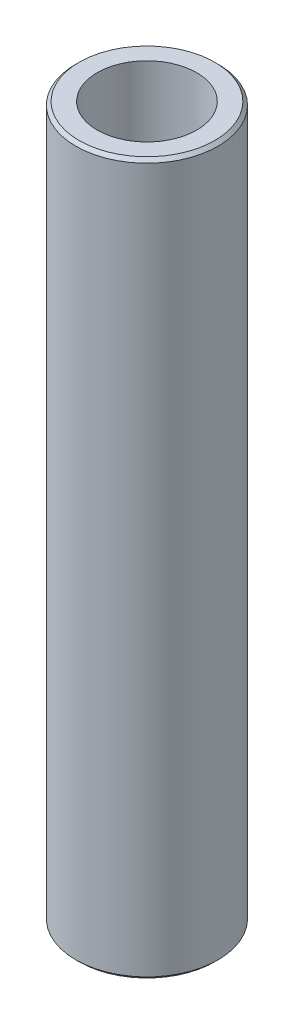
SolidWorks part; units mm, degrees
ref_plane "Front Plane" through (0, 0, 0) normal (0, 0, 1) x (1, 0, 0)
ref_plane "Top Plane" through (0, 0, 0) normal (0, 1, 0) x (1, 0, 0)
ref_plane "Right Plane" through (0, 0, 0) normal (1, 0, 0) x (0, 0, -1)
sketch "Sketch1" plane through (0, 0, 0) normal (0, 1, 0) x (1, 0, 0)
  circle A0 centre (0, 0) radius 60
  dimension "SHAFT_OD" = 120
extrude "Boss-Extrude1" add sketch "Sketch1" along normal blind 600
sketch "Sketch2" plane through (0, 0, 0) normal (0, 1, 0) x (1, 0, 0)
  circle A0 centre (0, 0) radius 41.98
  dimension "BORE_D" = 83.96
extrude "Cut-Extrude1" cut sketch "Sketch2" along normal through all
chamfer "Chamfer1" distance 2.7775 angle 45 2 edges at (0, 600, 60) (0, 0, 60)
